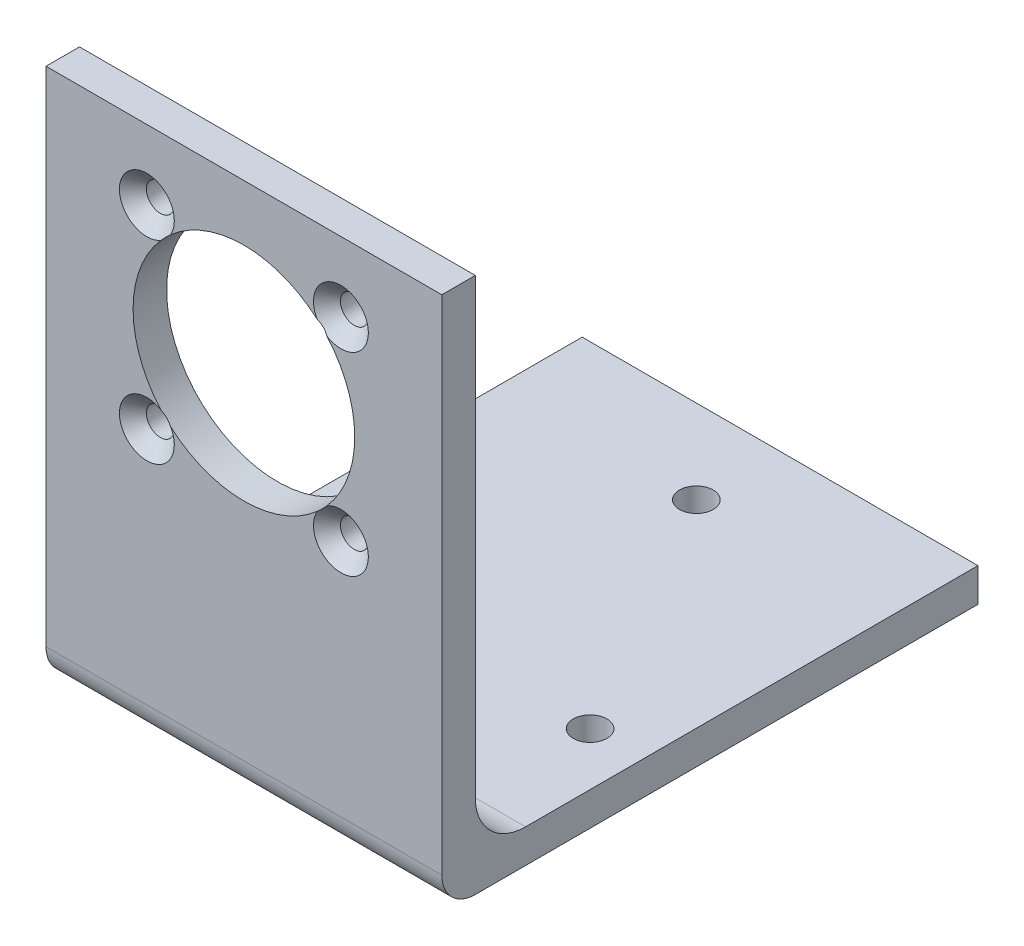
SolidWorks part; units mm, degrees
ref_plane "Front" through (0, 0, 0) normal (0, 0, 1) x (1, 0, 0)
ref_plane "Top" through (0, 0, 0) normal (0, 1, 0) x (1, 0, 0)
ref_plane "Right" through (0, 0, 0) normal (1, 0, 0) x (0, 0, -1)
sketch "Sketch1" plane through (0, 0, 0) normal (1, 0, 0) x (0, 0, -1)
  line L0 (0, 0) -> (0, 101.6)
  line L1 (0, 101.6) -> (6.35, 101.6)
  line L2 (6.35, 101.6) -> (6.35, 15.875)
  line L3 (15.875, 6.35) -> (101.6, 6.35)
  line L4 (101.6, 6.35) -> (101.6, 0)
  line L5 (101.6, 0) -> (0, 0)
  arc A0 (6.35, 15.875) -> (15.875, 6.35) centre (15.875, 15.875) ccw
  dimension "D3" = 9.525
  dimension "D1" = 101.6
  dimension "D2" = 6.35
  dimension "D4" = 85.725
extrude "Boss-Extrude1" add sketch "Sketch1" along normal blind 75
fillet "Fillet1" radius 6.35 1 edges at (37.5, 0, 0)
sketch "Sketch2" plane through (0, 0, 0) normal (0, 0, -1) x (-1, 0, 0)
  line L0 (-37.5, 15.875) -> (-37.5, 70) construction
  line L1 (-37.5, 70) -> (-55.8848, 88.3848) construction
  line L2 (-75, 0) -> (0, 0) construction
  line L4 (0, 15.875) -> (0, 101.6)
  line L5 (0, 101.6) -> (-75, 101.6)
  line L6 (-75, 101.6) -> (-75, 15.875)
  line L7 (-75, 15.875) -> (0, 15.875)
  line L8 (0, 15.875) -> (0, 101.6) construction
  line L9 (0, 101.6) -> (-75, 101.6) construction
  line L10 (-75, 101.6) -> (-75, 15.875) construction
  line L11 (-75, 15.875) -> (0, 15.875) construction
  circle A0 centre (-37.5, 70) radius 26 construction
  circle A1 centre (-37.5, 70) radius 21
  point P8 (-37.5, 96)
  dimension "D2" = 52
  dimension "D4" = 42
  dimension "D5" = 70
  dimension "D3" = 135
  dimension "D1" = 0
extrude "Cut-Extrude1" cut sketch "Sketch2" along normal blind 75
ref_axis "Axis1" through (37.5, 70, -6.35) along (0, 0, 1)
hole_wizard "CSK for M5 Flat Head Machine Screw3" positions "3DSketch8" profile "Sketch13" countersink size "M5" standard "ANSI Metric"
sketch3d "3DSketch8"
  point P0 (55.8848, 88.3848, 0)
sketch "Sketch13" plane through (55.8848, 88.3848, 0) normal (1, 0, 0) x (0, -1, 0)
  line L0 (0, 0) -> (0, 14.2923)
  line L1 (0, 14.2923) -> (2.65, 12.7)
  line L2 (2.65, 12.7) -> (2.65, 2.55)
  line L3 (2.65, 2.55) -> (5.2, 0)
  line L5 (5.2, 0) -> (0, 0)
  line L6 (-2.65, 2.55) -> (-5.2, 0) construction
  line L10 (0, 14.2923) -> (-2.65, 12.7) construction
  line L11 (0, -6.35) -> (0, 107.95) construction
  dimension "Hole Dia." = 5.3
  dimension "Hole Depth" = 12.7
  dimension "Near C'Sink Dia." = 10.4
  dimension "Near C'Sink Angle" = 90
  dimension "Drill Angle" = 118
pattern_circular "CirPattern1" count 4 over 360 about axis through (37.5, 70, -75) along (0, 0, 1) of "CSK for M5 Flat Head Machine Screw3"
sketch "Sketch8" plane through (0, 6.35, 0) normal (0, 1, 0) x (1, 0, 0)
  line L0 (37.5, 15.875) -> (37.5, 53.975) construction
  line L1 (37.5, 53.975) -> (0, 53.975) construction
  line L2 (0, 6.35) -> (0, 101.6) construction
  line L3 (65, 38.0979) -> (37.5, 85.7293) construction
  line L4 (0, 101.6) -> (0, 15.875)
  line L5 (0, 15.875) -> (75, 15.875)
  line L6 (75, 15.875) -> (75, 101.6)
  line L7 (75, 101.6) -> (0, 101.6)
  line L9 (0, 15.875) -> (75, 15.875) construction
  line L10 (75, 15.875) -> (75, 101.6) construction
  line L11 (75, 101.6) -> (0, 101.6) construction
  line L12 (37.5, 85.7293) -> (10, 38.0979) construction
  line L13 (10, 38.0979) -> (65, 38.0979) construction
  circle A0 centre (37.5, 53.975) radius 15.8771 construction
  dimension "D2" = 55
  dimension "D1" = 0
hole_wizard "M6 Clearance Hole1" positions "3DSketch4" profile "Sketch9" hole size "M6" standard "ANSI Metric" end condition through all
sketch3d "3DSketch4"
  point P0 (37.5, 6.35, -85.7293)
  point P3 (65, 6.35, -38.0979)
  point P6 (10, 6.35, -38.0979)
sketch "Sketch9" plane through (37.5, 6.35, -85.7293) normal (1, 0, 0) x (0, 0, 1)
  line L0 (0, 0) -> (0, 6.35)
  line L1 (0, 6.35) -> (3.2, 6.35)
  line L2 (3.2, 6.35) -> (3.2, 0)
  line L5 (3.2, 0) -> (0, 0)
  line L11 (0, -6.35) -> (0, 107.95) construction
  dimension "Thru Hole Dia." = 6.4
  dimension "Thru Hole Depth" = 6.35
